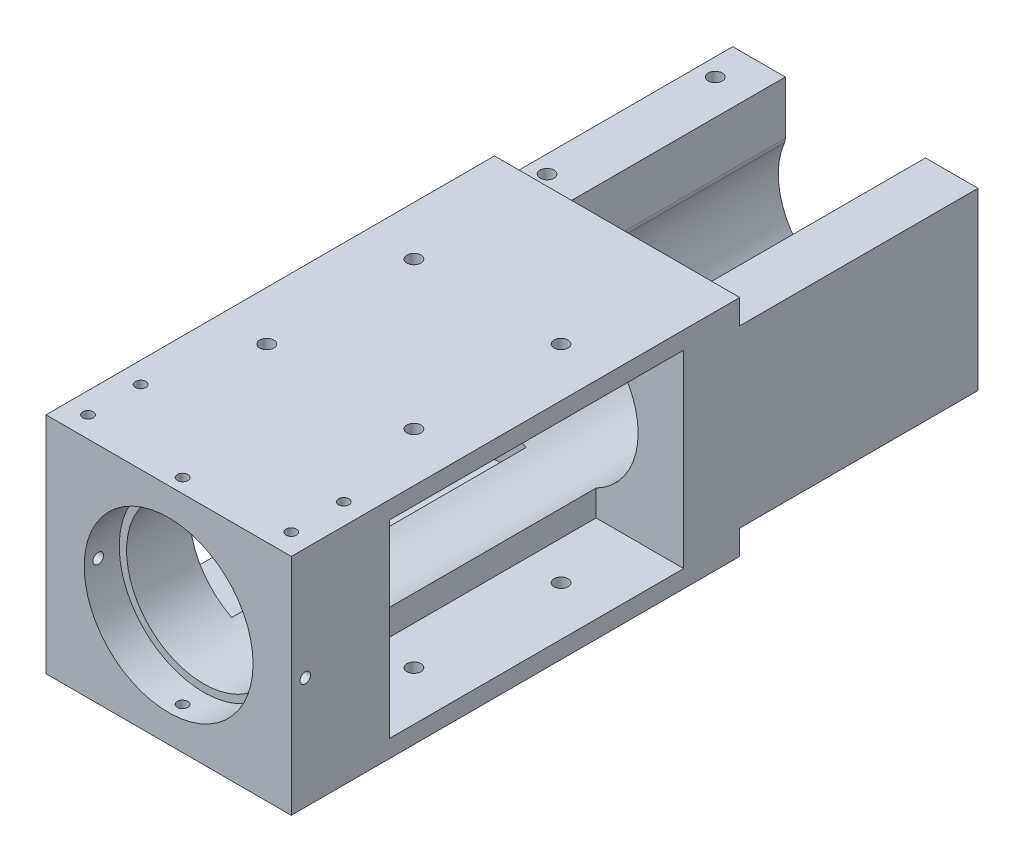
SolidWorks part; units mm, degrees
material "1060 合金"
ref_plane "前视基准面" through (0, 0, 0) normal (0, 0, 1) x (1, 0, 0)
ref_plane "上视基准面" through (0, 0, 0) normal (0, 1, 0) x (1, 0, 0)
ref_plane "右视基准面" through (0, 0, 0) normal (1, 0, 0) x (0, 0, -1)
sketch "草图1" plane through (0, 0, 0) normal (0, 0, 1) x (1, 0, 0)
  line L1 (-35, -32) -> (35, -32)
  line L2 (-35, -32) -> (-35, 32)
  line L3 (-35, 32) -> (35, 32)
  line L4 (35, -32) -> (35, 32)
  line L5 (-35, -32) -> (35, 32) construction
  line L6 (-35, 32) -> (35, -32) construction
  point P0 (0, 0)
  dimension "D1" = 70
  dimension "D2" = 64
extrude "凸台-拉伸1" add sketch "草图1" along normal mid plane 140
sketch "草图2" plane through (0, 0, 70) normal (0, 0, 1) x (1, 0, 0)
  circle A0 centre (0, 0) radius 24.1
  dimension "D1" = 48.2
extrude "切除-拉伸1" cut sketch "草图2" against normal blind 10
sketch "草图3" plane through (0, 32, 0) normal (0, 1, 0) x (1, 0, 0)
  line L0 (35, -70) -> (-35, -70) construction
  circle A0 centre (0, -66) radius 1.5
  point P5 (0, -70)
  dimension "D1" = 3
  dimension "D2" = 4
extrude "切除-拉伸2" cut sketch "草图3" against normal through all
sketch "草图4" plane through (35, 0, 0) normal (1, 0, 0) x (0, 0, -1)
  line L0 (-70, -32) -> (-70, 32) construction
  circle A0 centre (-66, 0) radius 1.5
  dimension "D1" = 3
  dimension "D2" = 4
extrude "切除-拉伸3" cut sketch "草图4" against normal through all
sketch "草图5" plane through (0, 0, 60) normal (0, 0, 1) x (1, 0, 0)
  circle A0 centre (0, 0) radius 22
  dimension "D1" = 44
extrude "切除-拉伸4" cut sketch "草图5" against normal through all
sketch "草图6" plane through (35, 0, 0) normal (1, 0, 0) x (0, 0, -1)
  line L1 (-42, -27) -> (42, -27)
  line L2 (-42, -27) -> (-42, 27)
  line L3 (-42, 27) -> (42, 27)
  line L4 (42, -27) -> (42, 27)
  line L5 (-42, -27) -> (42, 27) construction
  line L6 (-42, 27) -> (42, -27) construction
  point P0 (0, 0)
  point P5 (0, 0)
  dimension "D1" = 54
  dimension "D2" = 84
extrude "切除-拉伸5" cut sketch "草图6" against normal blind 25
mirror "镜向4" about plane through (0, 0, 0) normal (1, 0, 0) of "切除-拉伸5"
sketch "草图7" plane through (0, 32, 0) normal (0, 1, 0) x (1, 0, 0)
  line L0 (-21, 21) -> (21, 21) construction
  circle A0 centre (-21, 21) radius 2
  circle A1 centre (21, 21) radius 2
  point P4 (0, 21)
  dimension "D1" = 4
  dimension "D2" = 42
  dimension "D3" = 21
extrude "切除-拉伸6" cut sketch "草图7" against normal blind 20
sketch "草图8" plane through (0, 27, 0) normal (0, -1, 0) x (1, 0, 0)
  circle A1 centre (21, -21) radius 2 construction
  circle A2 centre (21, -21) radius 5.5
  circle A3 centre (21, -21) radius 5.5
  circle A4 centre (21, -21) radius 2
  circle M2 centre (21, -21) radius 2
  dimension "D1" = 3.5
extrude "切除-拉伸7" [suppressed] cut sketch "草图8" against normal blind 7 contours A3 M2
mirror "镜向1" [suppressed] about plane through (0, 0, 0) normal (1, 0, 0)
mirror "镜向2" about plane through (0, 0, 0) normal (0, 0, 1) of "镜向1", "切除-拉伸7", "切除-拉伸6"
sketch "草图9" plane through (0, 0, 0) normal (1, 0, 0) x (0, 0, -1)
  line L0 (-112.2479, 0) -> (108.0194, 0)
sketch "草图10" plane through (0, 0, -70) normal (0, 0, -1) x (-1, 0, 0)
  circle A0 centre (0, 0) radius 22 construction
  point P0 (0, -22)
sketch "草图11" plane through (0, 32, 0) normal (0, 1, 0) x (1, 0, 0)
  line L0 (-29, -64) -> (29, -64) construction
  line L1 (35, -70) -> (-35, -70) construction
  line L2 (-29, -49) -> (29, -49) construction
  circle A0 centre (-29, -64) radius 1.5
  circle A1 centre (29, -64) radius 1.5
  circle A2 centre (-29, -49) radius 1.5
  circle A3 centre (29, -49) radius 1.5
  point P4 (0, -64)
  point P7 (0, -70)
  point P12 (0, -49)
  dimension "D3" = 3
  dimension "D1" = 58
  dimension "D2" = 6
  dimension "D4" = 15
extrude "切除-拉伸8" cut sketch "草图11" against normal blind 10
sketch "草图12" plane through (35, 0, 0) normal (1, 0, 0) x (0, 0, -1)
  line L0 (-70, -32) -> (70, -32) construction
  line L1 (58, -32) -> (70, -32)
  line L2 (58, -32) -> (58, 32)
  line L3 (58, 32) -> (70, 32)
  line L4 (70, -32) -> (70, 32)
  line L5 (58, -32) -> (70, 32) construction
  line L6 (58, 32) -> (70, -32) construction
  point P0 (64, 0)
  point P6 (64, -32)
  dimension "D2" = 12
extrude "切除-拉伸9" cut sketch "草图12" against normal through all
sketch "草图13" plane through (0, 0, -58) normal (0, 0, -1) x (-1, 0, 0)
  line L0 (35, 32) -> (35, -32) construction
  line L1 (-35, -25) -> (35, -25)
  line L2 (-35, -25) -> (-35, 25)
  line L3 (-35, 25) -> (35, 25)
  line L4 (35, -25) -> (35, 25)
  line L5 (-35, -25) -> (35, 25) construction
  line L6 (-35, 25) -> (35, -25) construction
  circle A0 centre (0, 0) radius 22 construction
  circle A1 centre (0, 0) radius 22
  point P0 (0, 0)
  dimension "D1" = 50
extrude "凸台-拉伸2" add sketch "草图13" along normal blind 68
sketch "草图14" plane through (0, 25, 0) normal (0, 1, 0) x (1, 0, 0)
  line L0 (-35, 58) -> (35, 58) construction
  line L1 (20, 126) -> (-20, 126)
  line L2 (20, 126) -> (20, 58)
  line L3 (20, 58) -> (-20, 58)
  line L4 (-20, 126) -> (-20, 58)
  line L5 (20, 126) -> (-20, 58) construction
  line L6 (20, 58) -> (-20, 126) construction
  line L7 (-35, 126) -> (35, 126) construction
  point P0 (0, 92)
  point P7 (0, 126)
  point P12 (0, 58)
  dimension "D1" = 40
extrude "切除-拉伸10" cut sketch "草图14" against normal blind 20
fillet "圆角1" radius 3 2 edges at (-20, 9.1652, -92) (20, 9.1652, -92)
sketch "草图15" plane through (0, 25, 0) normal (0, 1, 0) x (1, 0, 0)
  line L0 (-30, 68) -> (-30, 116) construction
  line L1 (-35, 126) -> (-35, 58) construction
  line L2 (-35, 126) -> (-20, 126) construction
  circle A0 centre (-30, 68) radius 2
  circle A1 centre (-30, 116) radius 2
  dimension "D1" = 4
  dimension "D2" = 48
  dimension "D3" = 5
  dimension "D4" = 10
extrude "切除-拉伸11" cut sketch "草图15" against normal blind 10 contours A1 | A0 region at (-30, 25, -116)
mirror "镜向3" about plane through (0, 0, 0) normal (0, 1, 0) of "镜向1", "切除-拉伸7", "切除-拉伸6", "镜向2"
sketch "草图16" plane through (0, -32, 0) normal (0, -1, 0) x (1, 0, 0)
  line L0 (27, -48) -> (-27, -48) construction
  line L1 (-27, -48) -> (-27, 62) construction
  line L2 (-27, 62) -> (27, 62) construction
  line L3 (27, 62) -> (27, -48) construction
  line L4 (-35, 70) -> (35, 70) construction
  circle A0 centre (27, 62) radius 2
  circle A1 centre (-27, 62) radius 2
  circle A2 centre (27, -48) radius 2
  circle A3 centre (-27, -48) radius 2
  point P8 (0, 62)
  point P11 (0, 70)
  dimension "D1" = 4
  dimension "D2" = 110
  dimension "D3" = 54
  dimension "D4" = 8
extrude "切除-拉伸12" cut sketch "草图16" against normal blind 8
